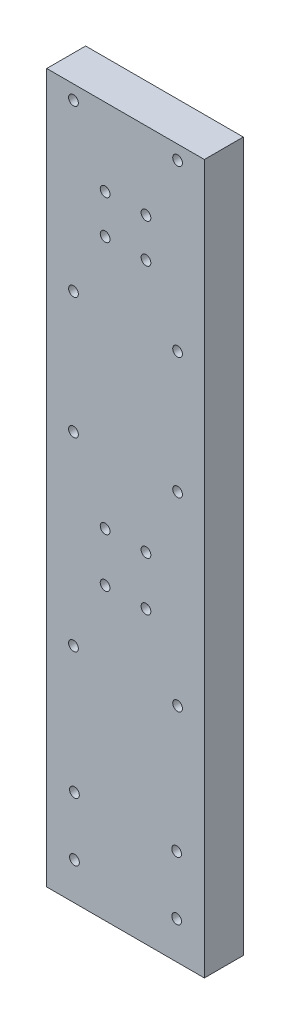
SolidWorks part; units mm, degrees
ref_plane "Front Plane" through (0, 0, 0) normal (0, 0, 1) x (1, 0, 0)
ref_plane "Top Plane" through (0, 0, 0) normal (0, 1, 0) x (1, 0, 0)
ref_plane "Right Plane" through (0, 0, 0) normal (1, 0, 0) x (0, 0, -1)
sketch "Sketch1" plane through (0, 0, 0) normal (0, 0, 1) x (1, 0, 0)
  line L4 (0, 0) -> (0, 72.8464)
  line L5 (0, 0) -> (16.2, 0)
  line L6 (0, 72.8464) -> (16.2, 72.8464)
  line L7 (16.2, 72.8464) -> (16.2, 0)
  circle A16 centre (6, 29.8464) radius 0.5
  circle A17 centre (10.2, 29.8464) radius 0.5
  circle A18 centre (10.2, 34.8929) radius 0.5
  circle A19 centre (10.2, 60.8929) radius 0.5
  circle A20 centre (13.45, 54.3929) radius 0.5
  circle A21 centre (6, 60.8929) radius 0.5
  circle A22 centre (6, 34.8929) radius 0.5
  circle A23 centre (2.75, 41.8929) radius 0.5
  circle A24 centre (2.85, 9.8464) radius 0.5
  circle A25 centre (13.35, 9.8464) radius 0.5
  circle A26 centre (13.35, 3.8464) radius 0.5
  circle A27 centre (2.85, 3.8464) radius 0.5
  circle A28 centre (13.45, 41.8929) radius 0.5
  circle A29 centre (2.75, 54.3929) radius 0.5
  circle A30 centre (13.45, 22.8464) radius 0.5
  circle A31 centre (2.75, 22.8464) radius 0.5
  circle A32 centre (10.2, 64.8929) radius 0.5
  circle A33 centre (13.45, 71.3929) radius 0.5
  circle A34 centre (6, 64.8929) radius 0.5
  circle A35 centre (2.75, 71.3929) radius 0.5
extrude "Boss-Extrude1" add sketch "Sketch1" along normal blind 4
